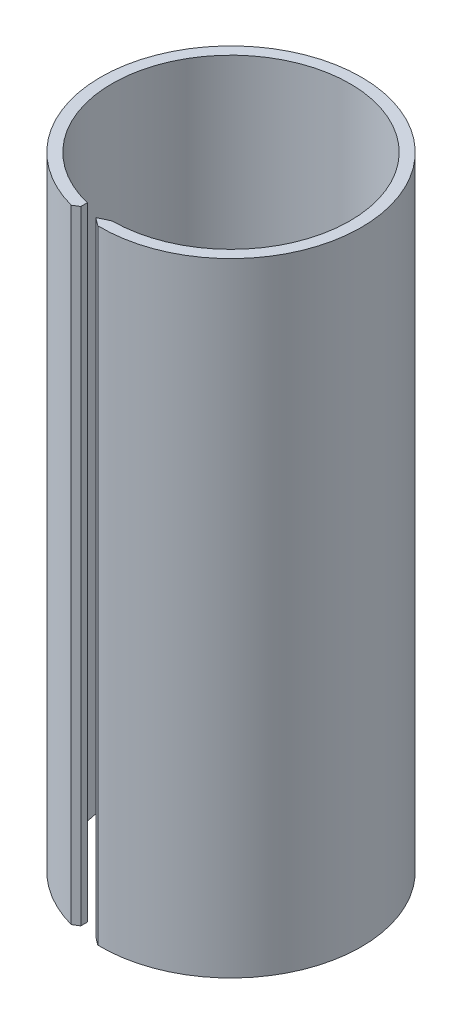
SolidWorks part; units mm, degrees
ref_plane "Front" through (0, 0, 0) normal (0, 0, 1) x (1, 0, 0)
ref_plane "Top" through (0, 0, 0) normal (0, 1, 0) x (1, 0, 0)
ref_plane "Right" through (0, 0, 0) normal (1, 0, 0) x (0, 0, -1)
sketch "Sketch1" plane through (0, 0, 0) normal (0, 1, 0) x (1, 0, 0)
  line L0 (0, 0) -> (0, -21)
  line L1 (0, -21) -> (-3.5842, -22.719)
  line L7 (-3.5769, -20.6931) -> (-6.0148, -22.1996)
  line L8 (-3.5769, -20.6931) -> (-0.5176, -22.9942)
  line L9 (-4.9668, -20.4042) -> (-4.9668, -22.4573)
  circle A1 centre (0, 0) radius 21
  circle A2 centre (0, 0) radius 23
  dimension "D1" = 46
  dimension "D2" = 42
extrude "Boss-Extrude1" add sketch "Sketch1" along normal blind 110 contours L1 A2 L7 A1 region at (15.3092, 0, 15.3092)
